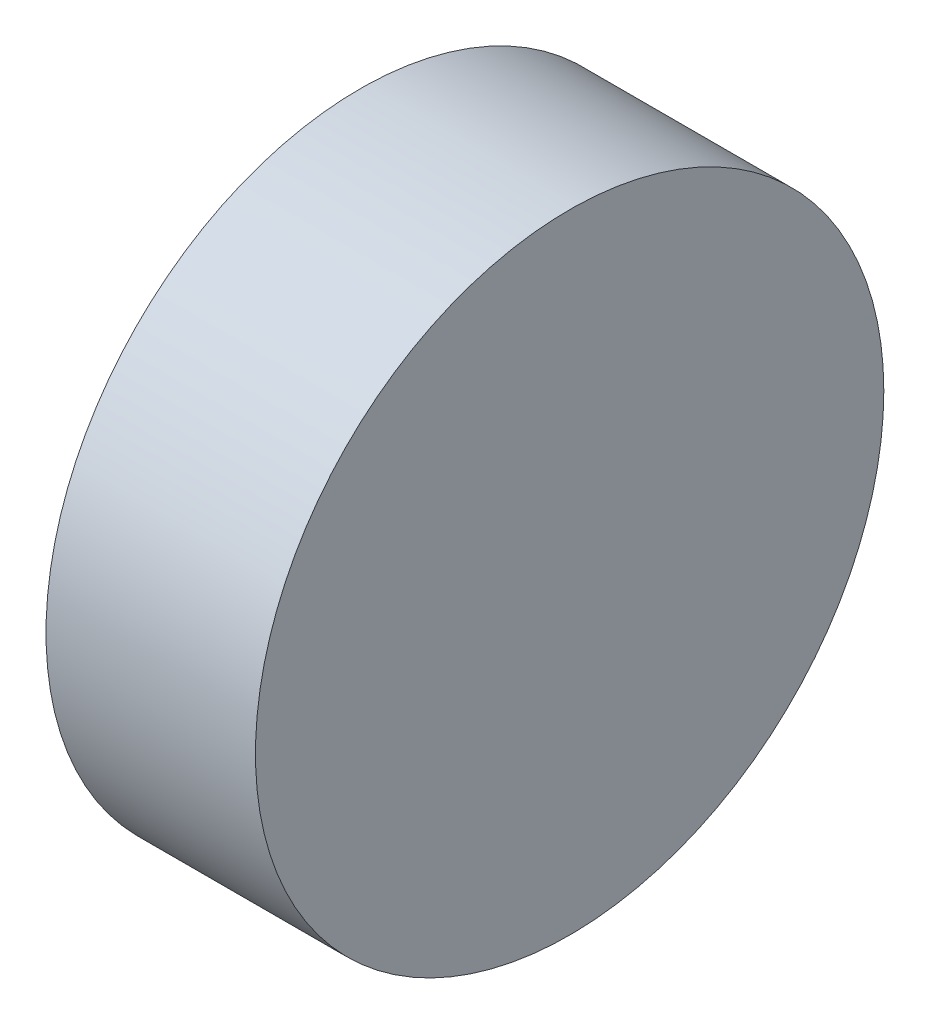
SolidWorks part; units mm, degrees
ref_plane "Front Plane" through (0, 0, 0) normal (0, 0, 1) x (1, 0, 0)
ref_plane "Top Plane" through (0, 0, 0) normal (0, 1, 0) x (1, 0, 0)
ref_plane "Right Plane" through (0, 0, 0) normal (1, 0, 0) x (0, 0, -1)
sketch "Sketch1" plane through (0, 0, 0) normal (1, 0, 0) x (0, 0, -1)
  circle A0 centre (0, 0) radius 38.1
  dimension "D1" = 76.2
extrude "Boss-Extrude1" add sketch "Sketch1" along normal blind 12.7 and the other way blind 12.7
